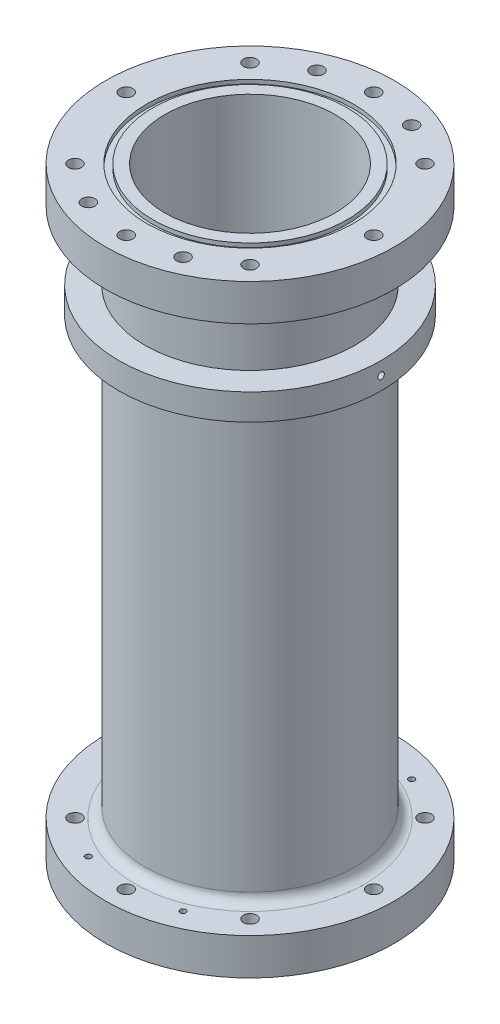
SolidWorks part; units mm, degrees
ref_plane "Front Plane" through (0, 0, 0) normal (0, 0, 1) x (1, 0, 0)
ref_plane "Top Plane" through (0, 0, 0) normal (0, 1, 0) x (1, 0, 0)
ref_plane "Right Plane" through (0, 0, 0) normal (1, 0, 0) x (0, 0, -1)
sketch "Sketch2" plane through (0, 0, 0) normal (0, 1, 0) x (1, 0, 0)
  circle A0 centre (0, 0) radius 41.275
  circle A1 centre (0, 0) radius 50.8
  dimension "D1" = 101.6
  dimension "D2" = 82.55
extrude "Base Cylinder" add sketch "Sketch2" along normal blind 292.1
sketch "Sketch3" plane through (0, 0, 0) normal (0, -1, 0) x (1, 0, 0)
  circle A0 centre (0, 0) radius 41.275
  circle A1 centre (0, 0) radius 69.85
  dimension "D1" = 139.7
extrude "Aft Flange" add sketch "Sketch3" against normal blind 17.78
sketch "Sketch4" plane through (0, 292.1, 0) normal (0, 1, 0) x (1, 0, 0)
  circle A0 centre (0, 0) radius 41.275
  circle A1 centre (0, 0) radius 69.85
extrude "Forward Flange" add sketch "Sketch4" against normal blind 17.78
sketch "Sketch6" plane through (0, 0, 0) normal (0, -1, 0) x (1, 0, 0)
  circle A0 centre (0, 0) radius 50.0761
  circle A1 centre (0, 0) radius 47.0027
  dimension "D1" = 100.1522
  dimension "D2" = 94.0054
extrude "O-Ring Slot 1" cut sketch "Sketch6" against normal blind 1.9812
sketch "Sketch7" plane through (0, 292.1, 0) normal (0, 1, 0) x (1, 0, 0)
  circle A0 centre (0, 0) radius 50.0761
  circle A1 centre (0, 0) radius 47.0027
  dimension "D1" = 100.1522
  dimension "D2" = 94.0054
extrude "O-Ring Slot 2" cut sketch "Sketch7" against normal blind 1.9812
sketch "Sketch8" plane through (0, 0, 0) normal (0, -1, 0) x (1, 0, 0)
  circle A0 centre (-59.9186, 0) radius 3.175
  circle A1 centre (-42.3688, 42.3688) radius 3.175
  circle A2 centre (0, 59.9186) radius 3.175
  circle A3 centre (42.3688, 42.3688) radius 3.175
  circle A4 centre (59.9186, 0) radius 3.175
  circle A5 centre (42.3688, -42.3688) radius 3.175
  circle A6 centre (0, -59.9186) radius 3.175
  circle A7 centre (-42.3688, -42.3688) radius 3.175
  point P36 (0, 0)
  dimension "D2" = 6.35
  dimension "D1" = 59.9186
  dimension "D3" = 8
extrude "Cut-Extrude4" cut sketch "Sketch8" against normal through all both and the other way through all
fillet "Fillet1" radius 4.7625 2 edges at (0, 17.78, -50.8) (0, 274.32, 50.8)
sketch "Sketch9" plane through (0, 292.1, 0) normal (0, 1, 0) x (1, 0, 0)
  line L0 (0, -76.2) -> (0, 76.2) construction
  line L1 (-32.6024, 78.7092) -> (32.6024, -78.7092) construction
  line L2 (-32.0538, -77.3847) -> (32.0538, 77.3847) construction
  circle A0 centre (0, 0) radius 59.9186 construction
  circle A1 centre (-22.9299, 55.3576) radius 3.175
  circle A2 centre (22.9299, -55.3576) radius 3.175
  circle A3 centre (22.9299, 55.3576) radius 3.175
  circle A4 centre (-22.9299, -55.3576) radius 3.175
  point P6 (0, 0)
  point P9 (0, 0)
  point P16 (0, 0)
  dimension "D1" = 119.8372
  dimension "D3" = 6.35
  dimension "D4" = 6.35
  dimension "D5" = 6.35
  dimension "D6" = 6.35
  dimension "D2" = 22.5
  dimension "D7" = 22.5
extrude "Cut-Extrude5" cut sketch "Sketch9" against normal blind 7.62
sketch "Sketch10" plane through (0, 0, 0) normal (0, -1, 0) x (1, 0, 0)
  line L0 (0, -76.2) -> (0, 76.2) construction
  line L1 (-33.7592, 81.5019) -> (33.7592, -81.5019) construction
  line L2 (-33.8465, -81.7128) -> (33.8465, 81.7128) construction
  circle A0 centre (0, 0) radius 59.9186 construction
  circle A1 centre (-22.9299, 55.3576) radius 3.175
  circle A2 centre (22.9299, -55.3576) radius 3.175
  circle A3 centre (22.9299, 55.3576) radius 3.175
  circle A4 centre (-22.9299, -55.3576) radius 3.175
  point P6 (0, 0)
  point P9 (0, 0)
  point P16 (0, 0)
  dimension "D1" = 119.8372
  dimension "D2" = 6.35
  dimension "D3" = 6.35
  dimension "D5" = 6.35
  dimension "D6" = 6.35
  dimension "D4" = 22.5
  dimension "D7" = 22.5
extrude "Cut-Extrude6" cut sketch "Sketch10" against normal blind 7.62
sketch "Sketch11" plane through (0, 284.48, 0) normal (0, 1, 0) x (1, 0, 0)
  circle A0 centre (-22.9299, 55.3576) radius 1.4097
  circle A1 centre (22.9299, 55.3576) radius 1.4097
  circle A2 centre (-22.9299, -55.3576) radius 1.4097
  circle A3 centre (22.9299, -55.3576) radius 1.4097
  dimension "D1" = 2.8194
  dimension "D2" = 2.8194
  dimension "D3" = 2.8194
  dimension "D4" = 2.8194
extrude "Cut-Extrude7" cut sketch "Sketch11" against normal up to next
sketch "Sketch12" plane through (0, 7.62, 0) normal (0, -1, 0) x (1, 0, 0)
  circle A0 centre (-22.9299, 55.3576) radius 1.4097
  circle A1 centre (22.9299, 55.3576) radius 1.4097
  circle A2 centre (-22.9299, -55.3576) radius 1.4097
  circle A3 centre (22.9299, -55.3576) radius 1.4097
  dimension "D1" = 2.8194
  dimension "D2" = 2.8194
  dimension "D3" = 2.8194
  dimension "D4" = 2.8194
extrude "Cut-Extrude8" cut sketch "Sketch12" against normal up to next
ref_plane "Plane1" through (-63.5, 0, 0) normal (1, 0, 0) x (0, 0, -1)
ref_plane "Plane2" through (0, 228.6, 0) normal (0, 1, 0) x (1, 0, 0)
sketch "Sketch14" plane through (0, 228.6, 0) normal (0, 1, 0) x (1, 0, 0)
  circle A0 centre (0, 0) radius 63.5
  circle A1 centre (0, 0) radius 50.8
  dimension "D1" = 101.6
  dimension "D2" = 127
extrude "Boss-Extrude1" add sketch "Sketch14" along normal blind 12.7
sketch "Sketch16" plane through (-63.5, 0, 0) normal (1, 0, 0) x (0, 0, -1)
  line L0 (63.5, 241.3) -> (-63.5, 241.3) construction
  circle A0 centre (0, 234.95) radius 1.5875
  dimension "D1" = 3.175
  dimension "D2" = 6.35
extrude "Cut-Extrude10" cut sketch "Sketch16" along normal blind 12.7
ref_plane "Plane3" through (63.5, 0, 0) normal (1, 0, 0) x (0, 0, -1)
sketch "Sketch17" plane through (63.5, 0, 0) normal (1, 0, 0) x (0, 0, -1)
  line L0 (63.5, 241.3) -> (-63.5, 241.3) construction
  circle A0 centre (0, 234.95) radius 1.5875
  dimension "D1" = 3.175
  dimension "D2" = 6.35
extrude "Cut-Extrude11" cut sketch "Sketch17" against normal blind 12.7
